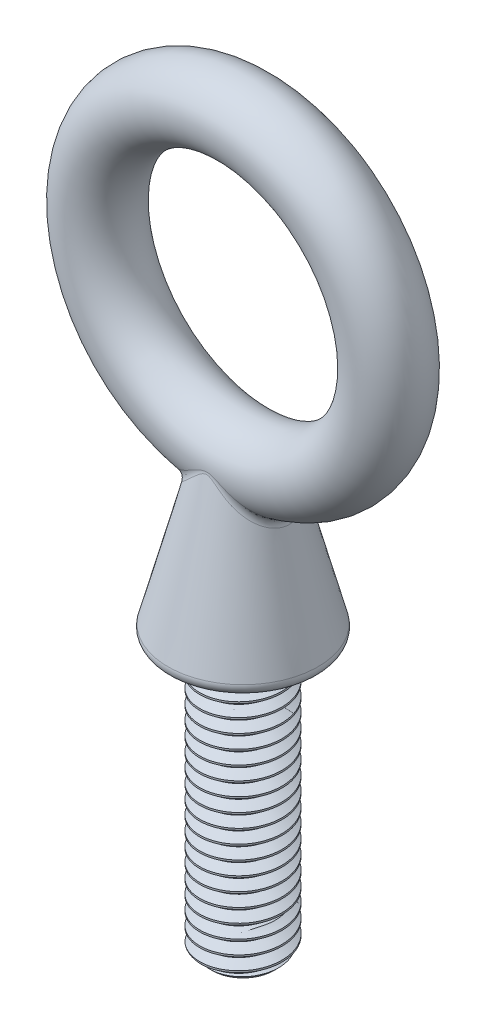
SolidWorks part; units mm, degrees
note: '?' marks a value the reader was unsure of.
ref_plane "Front Plane" through (0, 0, 0) normal (0, 0, 1) x (1, 0, 0)
ref_plane "Top Plane" through (0, 0, 0) normal (0, 1, 0) x (1, 0, 0)
ref_plane "Right Plane" through (0, 0, 0) normal (1, 0, 0) x (0, 0, -1)
sketch "Sketch1" plane through (0, 0, 0) normal (0, 0, 1) x (1, 0, 0)
  line L0 (0, -21.0344) -> (0, -67.0719) construction
  line L1 (-4.7625, -67.0719) -> (4.7625, -67.0719) construction
  line L2 (4.9344, -66.9727) -> (4.9344, -68.5602) construction
  line L3 (0, -21.0344) -> (0, -12.7) construction
  line L4 (-8.7312, -35.3219) -> (8.7313, -35.3219) construction
  line L5 (4.9344, -68.5602) -> (3.5595, -67.7664) construction
  line L6 (3.5595, -67.7664) -> (4.9344, -66.9727) construction
  line L7 (3.5595, -67.7664) -> (3.7314, -67.7664) construction
  line L8 (4.9344, -67.7664) -> (4.7625, -67.7664) construction
  line L9 (3.7314, -67.8656) -> (3.7314, -67.6672) construction
  line L10 (4.7625, -68.4609) -> (4.7625, -67.0719) construction
  line L11 (4.8484, -68.5105) -> (4.8484, -67.0223) construction
  circle A0 centre (0, 0) radius 21.0344 construction
  circle A1 centre (0, 16.8672) radius 4.1672 construction
  circle A2 centre (0, 0) radius 12.7 construction
  point P7 (0, -21.0344)
  point P9 (0, -35.3219)
  point P10 (0, 21.0344)
  point P11 (0, 12.7)
  point P14 (0, -67.0719)
  point P17 (0, 0)
  point P19 (0, -16.8672)
  point P21 (0, -35.3219)
  point P32 (3.7314, -67.7664)
  point P35 (4.7625, -67.7664)
  point P38 (4.8484, -67.7664)
  dimension "Pitch" = 1.5875
  dimension "D1" = 0.1984
sketch "Sketch2" plane through (0, 0, 0) normal (0, 1, 0) x (1, 0, 0)
  circle A0 centre (0, 0) radius 4.7625
extrude "Boss-Extrude1" add sketch "Sketch2" against normal up to vertex (67.0719 mm away) from vertex at -35.3219 starting at point (0, -35.3219, 0)
sketch "Sketch3" plane through (0, -67.0719, 0) normal (0, -1, 0) x (1, 0, 0)
  circle A1 centre (0, 0) radius 4.7625
  circle A2 centre (0, 0) radius 4.7625
  point P0 (4.7625, 0)
  point P1 (0, -4.7625)
  dimension "D1" = 0
sketch "Sketch4" plane through (0, 0, 0) normal (0, 0, 1) x (1, 0, 0)
  line L0 (3.7314, -67.6672) -> (3.7314, -67.8656)
  line L1 (3.7314, -67.8656) -> (4.8484, -68.5105)
  line L2 (4.8484, -68.5105) -> (4.8484, -67.0223)
  line L3 (4.8484, -67.0223) -> (3.7314, -67.6672)
sketch "Sketch5" plane through (0, -67.0719, 0) normal (0, -1, 0) x (1, 0, 0)
  circle A0 centre (0, 0) radius 3.5595
extrude "Cut-Extrude1" cut sketch "Sketch5" against normal through all draft 45 flip side to cut
sketch "Sketch6" plane through (0, 0, 0) normal (1, 0, 0) x (0, 0, -1)
  circle A0 centre (0, 16.8672) radius 4.1672
ref_axis "Axis1" through (0, 0, -7.6398) along (0, 0, 1)
revolve "Revolve1" add sketch "Sketch6" angle 360 about axis through (0, 0, -7.6398) along (0, 0, 1)
sketch "Sketch8" plane through (0, 0, 0) normal (0, 0, 1) x (1, 0, 0)
  line L0 (0, -35.3219) -> (0, -16.8672)
  line L1 (0, -16.8672) -> (-4.1672, -16.8672)
  line L2 (-7.6895, -35.3219) -> (-8.7312, -35.3219) construction
  line L3 (-8.7312, -35.3219) -> (-8.7312, -34.2801) construction
  line L4 (0, -35.3219) -> (8.7312, -35.3219) construction
  line L5 (-8.7312, -35.3219) -> (8.7313, -35.3219) construction
  line L6 (-8.6967, -34.014) -> (-4.1672, -16.8672)
  line L7 (-8.7312, -35.3219) -> (0, -35.3219) construction
  line L9 (-7.6895, -35.3219) -> (0, -35.3219)
  arc A0 (-8.6967, -34.014) -> (-7.6895, -35.3219) centre (-7.6895, -34.2801) ccw
  circle A1 centre (0, -16.8672) radius 4.1672 construction
  dimension "D1" = 1.0418
revolve "Revolve2" add sketch "Sketch8" angle 360 about L0
fillet "Fillet1" radius 1.0418 1 edges at (4.338, -19.8199, 2.3783)
sketch "SketchX" plane through (0, 0, 0) normal (1, 0, 0) x (0, 0, -1)
  line L0 (4.7625, -67.0719) -> (4.7625, -63.1031) construction
  line L1 (0, -67.0719) -> (4.7625, -67.0719) construction
  dimension "D1" = 3.9688
  dimension "D2" = 4.7625
ref_axis "Center Axis 1" through (0, 21.5506, 0) along (0, -1, 0)?
ref_axis "Center Axis 2" through (0, 0, -7.6398) along (0, 0, 1)?
curve "Helix/Spiral1" pitch 1.5875 height 33.3375 turns 21 parameters "Pitch"=1.5875
ref_plane "Plane1" through (0, -35.3219, 0) normal (0, -1, 0) x (1, 0, 0)
split "Split1" trim tools "Plane1" bodies to split 109 resulting bodies 110 111
sweep "Cut-Sweep1" cut profiles "Sketch4" path "Helix/Spiral1" align with end faces yes
sketch "Sketch9" plane through (0, -35.3219, 0) normal (0, -1, 0) x (1, 0, 0)
  line L0 (-8.7312, 0) -> (8.7313, 0) construction
  circle A0 centre (0, 0) radius 4.7625
extrude "Boss-Extrude2" add sketch "Sketch9" along normal blind 2.54 draft 45
equation "\"D3@Helix/Spiral1\" = \"Pitch@Helix/Spiral1\" + \"Thread Lg.@Sketch1\""
equation "\"D1@Sketch8\" = \"A@Sketch1\" / 8"
equation "\"D1@Fillet1\" = \"A@Sketch1\" / 8"
equation "\"D1@SketchX\"= \"Pitch@Helix/Spiral1\"*2.5"
equation "\"D1@Sketch1\"=\"Pitch@Sketch1\"/8"
equation "\"Pitch@Helix/Spiral1\"=\"Pitch@Sketch1\""
equation "\"D2@SketchX\" = \"Thread OD@Sketch1\" / 2"
